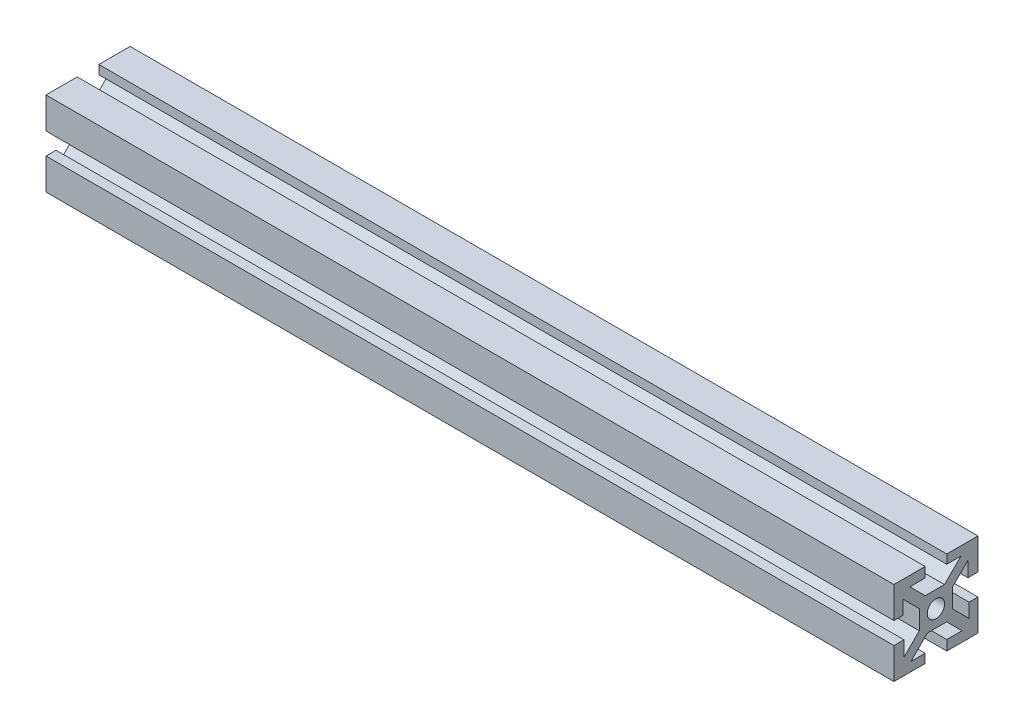
SolidWorks part; units mm, degrees
ref_plane "Front Plane" through (0, 0, 0) normal (0, 0, 1) x (1, 0, 0)
ref_plane "Top Plane" through (0, 0, 0) normal (0, 1, 0) x (1, 0, 0)
ref_plane "Right Plane" through (0, 0, 0) normal (1, 0, 0) x (0, 0, -1)
sketch "Sketch1" plane through (0, 0, 0) normal (1, 0, 0) x (0, 0, -1)
  line L0 (2.5534, 5) -> (7.4749, 9.9215)
  line L1 (-5, 5) -> (5, 5)
  line L2 (-5, 5) -> (-5, -5)
  line L3 (-5, -5) -> (5, -5)
  line L4 (5, 5) -> (5, -5)
  line L5 (-5, 5) -> (5, -5) construction
  line L6 (-5, -5) -> (5, 5) construction
  line L7 (7.4749, 9.9215) -> (9.5962, 7.8001)
  line L8 (9.5962, 7.8001) -> (5, 3.2039)
  line L9 (5, 5) -> (13.6489, 13.6489) construction
  line L10 (7.4749, 9.9215) -> (3.24, 9.9215)
  line L11 (3.24, 9.9215) -> (3.24, 12.5962)
  line L12 (3.24, 12.5962) -> (12.5962, 12.5962)
  line L13 (9.5962, 7.8001) -> (9.5962, 3.24)
  line L14 (9.5962, 3.24) -> (12.5962, 3.24)
  line L15 (12.5962, 3.24) -> (12.5962, 12.5962)
  line L17 (0, 0) -> (0, 24.089) construction
  line L18 (0, 0) -> (23.75, 0) construction
  circle A0 centre (0, 0) radius 2.605
  point P0 (0, 0)
  dimension "D1" = 5.21
  dimension "D2" = 10
  dimension "D3" = 10
  dimension "D4" = 3
  dimension "D5" = 1.27
  dimension "D6" = 6.5
  dimension "D7" = 3.24
  dimension "D8" = 3.24
  dimension "D9" = 3
extrude "Boss-Extrude1" add sketch "Sketch1" along normal blind 254 contours L4 L1 L2 L3 A0 | L8 L7 L0 L1 L4 | L14 L15 L12 L11 L10 L7 L13 region at (0, 4.8586, -3.7767) region at (0, 6.7479, -6.3823) region at (0, 9.18, -9.3105)
ref_axis "Axis1" through (0, 0, 0) along (1, 0, 0)
pattern_circular "CirPattern1" count 4 over 360 about axis through (0, 0, 0) along (1, 0, 0) of "Boss-Extrude1"
